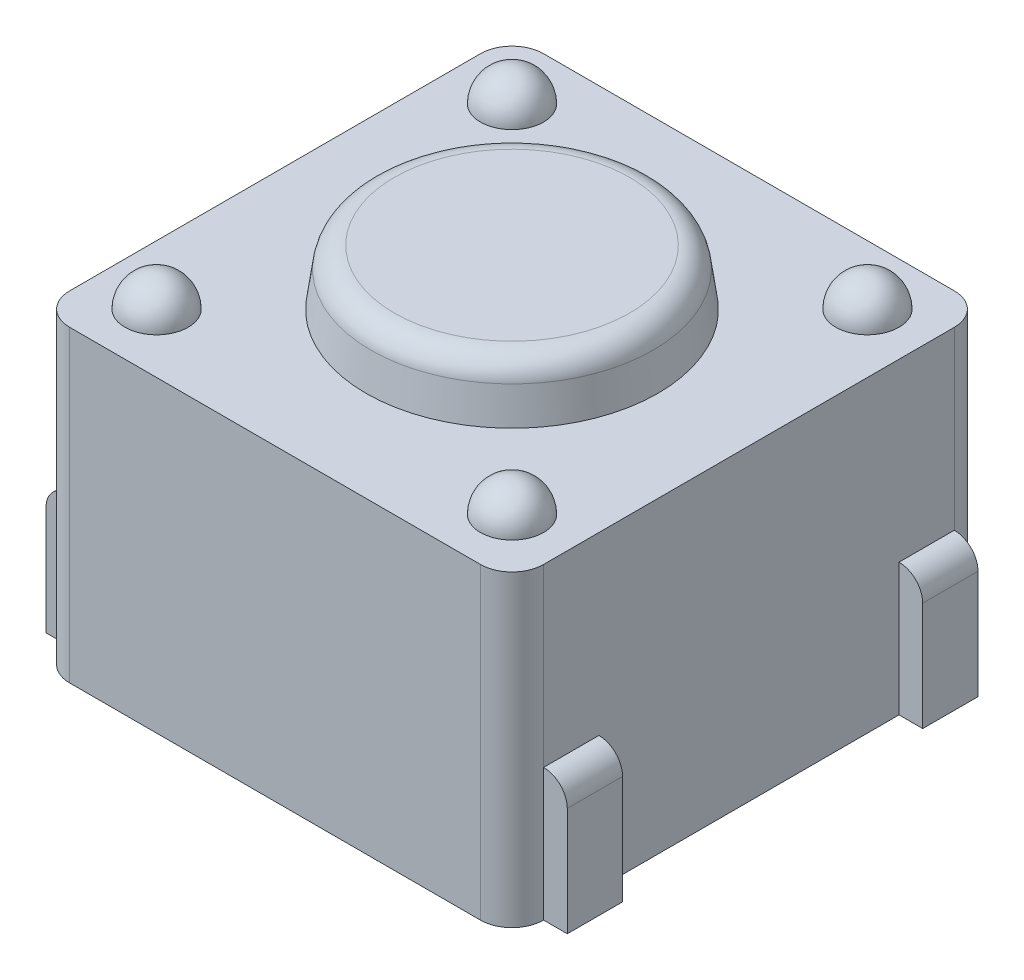
SolidWorks part; units mm, degrees
ref_plane "Front Plane" through (0, 0, 0) normal (0, 0, 1) x (1, 0, 0)
ref_plane "Top Plane" through (0, 0, 0) normal (0, 1, 0) x (1, 0, 0)
ref_plane "Right Plane" through (0, 0, 0) normal (1, 0, 0) x (0, 0, -1)
sketch "Sketch1" plane through (0, 0, 0) normal (0, 1, 0) x (1, 0, 0)
  line L0 (-3, -3) -> (3, -3)
  line L1 (-3, -3) -> (-3, 3)
  line L2 (3, -3) -> (3, 3)
  line L3 (-3, 3) -> (3, 3)
  line L4 (-3, -3) -> (3, 3) construction
  line L5 (3, -3) -> (-3, 3) construction
  point P1 (0, 0)
  dimension "D1" = 6
  dimension "D2" = 6
extrude "Boss-Extrude1" add sketch "Sketch1" along normal blind 3.9
sketch "Sketch2" plane through (3, 0, 0) normal (1, 0, 0) x (0, 0, -1)
  line L0 (-2.6, 0) -> (-1.9, 0)
  line L1 (-2.6, 0) -> (-2.6, 1.6749)
  line L2 (-1.9, 0) -> (-1.9, 1.6749)
  line L3 (-2.6, 1.6749) -> (-1.9, 1.6749)
  line L4 (-3, 0) -> (3, 0) construction
  point P6 (0, 0)
  dimension "D1" = 0.7
  dimension "D2" = 1.9
extrude "Boss-Extrude2" add sketch "Sketch2" along normal blind 0.3
sketch "Sketch3" plane through (0, 3.9, 0) normal (0, 1, 0) x (1, 0, 0)
  circle A0 centre (2.25, -2.25) radius 0.4
  dimension "D2" = 2.25
extrude "Boss-Extrude3" add sketch "Sketch3" along normal blind 0.4
mirror "Mirror1" about plane through (0, 0, 0) normal (0, 0, 1) of "Boss-Extrude3", "Boss-Extrude2"
mirror "Mirror2" about plane through (0, 0, 0) normal (1, 0, 0) of "Mirror1"
fillet "Fillet1" radius 0.4 4 edges at (-2.25, 4.3, 2.65) (-2.25, 4.3, -2.65) (2.25, 4.3, -2.65) (2.25, 4.3, 2.65)
fillet "Fillet2" radius 0.4 4 edges at (3, 1.95, -3) (-3, 1.95, -3) (-3, 1.95, 3) (3, 1.95, 3)
sketch "Sketch4" plane through (0, 3.9, 0) normal (0, 1, 0) x (1, 0, 0)
  circle A0 centre (0, 0) radius 1.75
extrude "Boss-Extrude4" add sketch "Sketch4" along normal blind 0.7
draft "Draft1" type of draft neutral plane draft angle 8 faces to draft 1 face at (0, 4.6, 1.75) neutral plane through (0, 4.6, 0) neutral plane normal (0, 1, 0) parameters "D1"=8
fillet "Fillet3" radius 0.3 1 edges at (0, 4.6, 1.75)
fillet "Fillet4" radius 0.3 4 edges at (-3.3, 1.6749, -2.25) (-3.3, 1.6749, 2.25) (3.3, 1.6749, -2.25) (3.3, 1.6749, 2.25)
